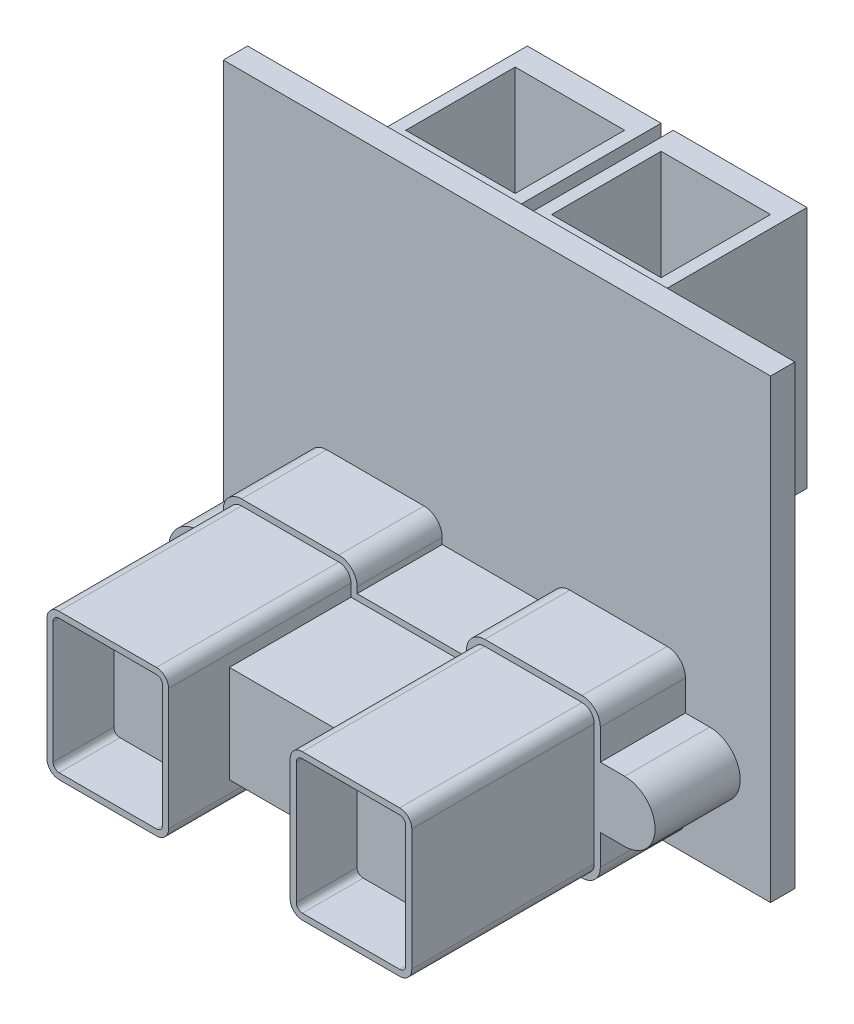
SolidWorks part; units mm, degrees
ref_plane "Front Plane" through (0, 0, 0) normal (0, 0, 1) x (1, 0, 0)
ref_plane "Top Plane" through (0, 0, 0) normal (0, 1, 0) x (1, 0, 0)
ref_plane "Right Plane" through (0, 0, 0) normal (1, 0, 0) x (0, 0, -1)
sketch "Sketch1" plane through (0, 0, 0) normal (0, 0, 1) x (1, 0, 0)
  line L1 (-22.5, 18.75) -> (22.5, 18.75)
  line L2 (-22.5, 18.75) -> (-22.5, -18.75)
  line L3 (-22.5, -18.75) -> (22.5, -18.75)
  line L4 (22.5, 18.75) -> (22.5, -18.75)
  line L5 (-22.5, 18.75) -> (22.5, -18.75) construction
  line L6 (-22.5, -18.75) -> (22.5, 18.75) construction
  point P0 (0, 0)
  dimension "D1" = 37.5
  dimension "D2" = 45
extrude "Boss-Extrude1" add sketch "Sketch1" along normal blind 2
sketch "Sketch2" plane through (0, 0, 2) normal (0, 0, 1) x (1, 0, 0)
  line L0 (0, 18.75) -> (0, -18.75) construction
  line L1 (22.5, 18.75) -> (-22.5, 18.75) construction
  line L2 (-22.5, -18.75) -> (22.5, -18.75) construction
  line L4 (-20, -4.75) -> (20, -4.75)
  line L5 (-20, -4.75) -> (-20, -17.75)
  line L6 (-20, -17.75) -> (20, -17.75)
  line L7 (20, -4.75) -> (20, -17.75)
  line L8 (-20, -4.75) -> (20, -17.75) construction
  line L9 (-20, -17.75) -> (20, -4.75) construction
  point P6 (0, -11.25)
  dimension "D1" = 13
  dimension "D2" = 40
  dimension "D3" = 1
extrude "Boss-Extrude2" add sketch "Sketch2" along normal blind 7
sketch "Sketch3" plane through (0, 0, 9) normal (0, 0, 1) x (1, 0, 0)
  line L0 (0, -4.75) -> (0, -17.75) construction
  line L1 (20, -4.75) -> (-20, -4.75) construction
  line L2 (-20, -17.75) -> (20, -17.75) construction
  line L3 (-5, -7.25) -> (-5, -5.25)
  line L4 (5, -5.25) -> (15, -5.25)
  line L5 (5, -7.25) -> (5, -5.25)
  line L6 (5, -17.25) -> (15, -17.25)
  line L7 (15, -5.25) -> (15, -17.25)
  line L8 (-5, -5.25) -> (-15, -5.25)
  line L9 (5, -15.25) -> (5, -17.25)
  line L10 (-5, -17.25) -> (-15, -17.25)
  line L11 (-15, -5.25) -> (-15, -17.25)
  line L12 (5, -7.25) -> (-5, -7.25)
  line L13 (-5, -15.25) -> (-5, -17.25)
  line L14 (5, -15.25) -> (-5, -15.25)
  line L15 (-20, -17.75) -> (20, -17.75) construction
  point P20 (0, -7.25)
  point P24 (0, -15.25)
  dimension "D1" = 0.5
  dimension "D2" = 0.5
  dimension "D3" = 30
  dimension "D5" = 10
  dimension "D6" = 2
  dimension "D7" = 2
extrude "Boss-Extrude3" add sketch "Sketch3" along normal blind 15
fillet "Fillet1" radius 1 8 edges at (-15, -17.25, 16.5) (-5, -17.25, 16.5) (5, -17.25, 16.5) (-15, -5.25, 16.5) (15, -17.25, 16.5) (15, -5.25, 16.5) (5, -5.25, 16.5) (-5, -5.25, 16.5)
sketch "Sketch4" plane through (0, 0, 24) normal (0, 0, 1) x (1, 0, 0)
  line L0 (-5.5, -14.75) -> (-5.5, -7.75)
  line L1 (5.5, -7.75) -> (5.5, -14.75)
  line L2 (5, -7.25) -> (5, -15.25)
  line L3 (5, -15.25) -> (-5, -15.25)
  line L4 (-5, -15.25) -> (-5, -7.25)
  line L5 (-5, -7.25) -> (5, -7.25)
  line L48 (-14.5, -6.25) -> (-14.5, -16.25)
  line L49 (-14, -16.75) -> (-6, -16.75)
  line L50 (-5.5, -16.25) -> (-5.5, -14.75)
  line L51 (-5.5, -14.75) -> (5.5, -14.75)
  line L52 (5.5, -14.75) -> (5.5, -16.25)
  line L53 (6, -16.75) -> (14, -16.75)
  line L54 (14.5, -16.25) -> (14.5, -6.25)
  line L55 (14, -5.75) -> (6, -5.75)
  line L56 (5.5, -6.25) -> (5.5, -7.75)
  line L57 (5.5, -7.75) -> (-5.5, -7.75)
  line L58 (-5.5, -7.75) -> (-5.5, -6.25)
  line L59 (-6, -5.75) -> (-14, -5.75)
  line L60 (-14.5, -6.25) -> (-14.5, -16.25)
  line L61 (-14, -16.75) -> (-6, -16.75)
  line L62 (-5.5, -16.25) -> (-5.5, -14.75)
  line L63 (-5.5, -14.75) -> (5.5, -14.75) construction
  line L64 (5.5, -14.75) -> (5.5, -16.25)
  line L65 (6, -16.75) -> (14, -16.75)
  line L66 (14.5, -16.25) -> (14.5, -6.25)
  line L67 (14, -5.75) -> (6, -5.75)
  line L68 (5.5, -6.25) -> (5.5, -7.75)
  line L69 (5.5, -7.75) -> (-5.5, -7.75) construction
  line L70 (-5.5, -7.75) -> (-5.5, -6.25)
  line L71 (-6, -5.75) -> (-14, -5.75)
  arc A32 (-14.5, -16.25) -> (-14, -16.75) centre (-14, -16.25) ccw
  arc A33 (-6, -16.75) -> (-5.5, -16.25) centre (-6, -16.25) ccw
  arc A34 (5.5, -16.25) -> (6, -16.75) centre (6, -16.25) ccw
  arc A35 (14, -16.75) -> (14.5, -16.25) centre (14, -16.25) ccw
  arc A36 (14.5, -6.25) -> (14, -5.75) centre (14, -6.25) ccw
  arc A37 (6, -5.75) -> (5.5, -6.25) centre (6, -6.25) ccw
  arc A38 (-5.5, -6.25) -> (-6, -5.75) centre (-6, -6.25) ccw
  arc A39 (-14, -5.75) -> (-14.5, -6.25) centre (-14, -6.25) ccw
  arc A40 (-14.5, -16.25) -> (-14, -16.75) centre (-14, -16.25) ccw
  arc A41 (-6, -16.75) -> (-5.5, -16.25) centre (-6, -16.25) ccw
  arc A42 (5.5, -16.25) -> (6, -16.75) centre (6, -16.25) ccw
  arc A43 (14, -16.75) -> (14.5, -16.25) centre (14, -16.25) ccw
  arc A44 (14.5, -6.25) -> (14, -5.75) centre (14, -6.25) ccw
  arc A45 (6, -5.75) -> (5.5, -6.25) centre (6, -6.25) ccw
  arc A46 (-5.5, -6.25) -> (-6, -5.75) centre (-6, -6.25) ccw
  arc A47 (-14, -5.75) -> (-14.5, -6.25) centre (-14, -6.25) ccw
  dimension "D1" = 0.5
extrude "Cut-Extrude1" cut sketch "Sketch4" against normal blind 5
sketch "Sketch5" plane through (0, 0, 9) normal (0, 0, 1) x (1, 0, 0)
  line L11 (-20, -4.75) -> (-20, -17.75) construction
  line L12 (20, -17.75) -> (20, -4.75) construction
  line L15 (-15.5, -6.25) -> (-15.5, -16.25)
  line L16 (-14, -17.75) -> (-6, -17.75)
  line L17 (6, -17.75) -> (14, -17.75)
  line L18 (-4.5, -15.75) -> (4.5, -15.75)
  line L19 (-4.5, -16.25) -> (-4.5, -15.75)
  line L20 (4.5, -15.75) -> (4.5, -16.25)
  line L21 (-14, -17.75) -> (-6, -17.75)
  line L22 (6, -17.75) -> (14, -17.75)
  line L23 (-4.5, -15.75) -> (4.5, -15.75)
  line L24 (-4.5, -16.25) -> (-4.5, -15.75)
  line L25 (4.5, -15.75) -> (4.5, -16.25)
  line L26 (-15.5, -6.25) -> (-15.5, -16.25) construction
  line L27 (-17.5, -8.75) -> (-15.5, -8.75)
  line L28 (15.5, -16.25) -> (15.5, -6.25)
  line L29 (15.5, -16.25) -> (15.5, -6.25) construction
  line L30 (-15.5, -8.75) -> (-15.5, -6.25)
  line L31 (-17.5, -13.75) -> (-15.5, -13.75)
  line L32 (-15.5, -13.75) -> (-15.5, -16.25)
  line L33 (17.5, -13.75) -> (15.5, -13.75)
  line L34 (15.5, -13.75) -> (15.5, -16.25)
  line L35 (17.5, -8.75) -> (15.5, -8.75)
  line L36 (15.5, -8.75) -> (15.5, -6.25)
  line L51 (20.5, -18.25) -> (20.5, -4.25)
  line L52 (-20.5, -18.25) -> (20.5, -18.25)
  line L53 (-20.5, -4.25) -> (-20.5, -18.25)
  line L54 (20.5, -4.25) -> (-20.5, -4.25)
  line L55 (20.5, -18.25) -> (20.5, -4.25)
  line L56 (-20.5, -18.25) -> (20.5, -18.25)
  line L57 (-20.5, -4.25) -> (-20.5, -18.25)
  line L58 (20.5, -4.25) -> (-20.5, -4.25)
  line L214 (14, -4.75) -> (6, -4.75)
  line L215 (4.5, -6.25) -> (4.5, -6.75)
  line L216 (4.5, -6.75) -> (-4.5, -6.75)
  line L217 (-4.5, -6.75) -> (-4.5, -6.25)
  line L218 (-6, -4.75) -> (-14, -4.75)
  line L219 (14, -4.75) -> (6, -4.75)
  line L220 (4.5, -6.25) -> (4.5, -6.75)
  line L221 (4.5, -6.75) -> (-4.5, -6.75)
  line L222 (-4.5, -6.75) -> (-4.5, -6.25)
  line L223 (-6, -4.75) -> (-14, -4.75)
  circle A4 centre (-17.5, -11.25) radius 2.5 construction
  circle A5 centre (17.5, -11.25) radius 2.5 construction
  arc A6 (-6, -17.75) -> (-4.5, -16.25) centre (-6, -16.25) ccw
  arc A7 (4.5, -16.25) -> (6, -17.75) centre (6, -16.25) ccw
  arc A8 (-6, -17.75) -> (-4.5, -16.25) centre (-6, -16.25) ccw
  arc A9 (4.5, -16.25) -> (6, -17.75) centre (6, -16.25) ccw
  arc A14 (-15.5, -16.25) -> (-14, -17.75) centre (-14, -16.25) ccw
  arc A15 (-14, -4.75) -> (-15.5, -6.25) centre (-14, -6.25) ccw
  arc A16 (-15.5, -16.25) -> (-14, -17.75) centre (-14, -16.25) ccw
  arc A17 (-14, -4.75) -> (-15.5, -6.25) centre (-14, -6.25) ccw
  arc A18 (-17.5, -13.75) -> (-17.5, -8.75) centre (-17.5, -11.25) cw
  arc A19 (17.5, -8.75) -> (17.5, -13.75) centre (17.5, -11.25) cw
  arc A20 (14, -17.75) -> (15.5, -16.25) centre (14, -16.25) ccw
  arc A21 (15.5, -6.25) -> (14, -4.75) centre (14, -6.25) ccw
  arc A22 (14, -17.75) -> (15.5, -16.25) centre (14, -16.25) ccw
  arc A23 (15.5, -6.25) -> (14, -4.75) centre (14, -6.25) ccw
  arc A85 (6, -4.75) -> (4.5, -6.25) centre (6, -6.25) ccw
  arc A86 (-4.5, -6.25) -> (-6, -4.75) centre (-6, -6.25) ccw
  arc A87 (6, -4.75) -> (4.5, -6.25) centre (6, -6.25) ccw
  arc A88 (-4.5, -6.25) -> (-6, -4.75) centre (-6, -6.25) ccw
  point P13 (-20, -11.25)
  dimension "D3" = 5
  dimension "D1" = 0.5
  dimension "D2" = 0.5
  dimension "D4" = 0.5
  dimension "D5" = 0.5
  dimension "D6" = 0.5
extrude "Cut-Extrude2" cut sketch "Sketch5" against normal up to surface (7 mm away) up to face at (0, 0, 2)
sketch "Sketch6" plane through (0, 0, 0) normal (0, 0, -1) x (-1, 0, 0)
  line L0 (0, 18.75) -> (0, -18.75) construction
  line L1 (-22.5, 18.75) -> (22.5, 18.75) construction
  line L2 (22.5, -18.75) -> (-22.5, -18.75) construction
  line L3 (-0.5, 18.25) -> (-0.5, -1.75)
  line L4 (-11.5, 18.25) -> (11.5, 18.25) construction
  line L5 (-11.5, 18.25) -> (-11.5, -1.75)
  line L6 (-11.5, -1.75) -> (11.5, -1.75) construction
  line L7 (11.5, 18.25) -> (11.5, -1.75)
  line L8 (-11.5, 18.25) -> (11.5, -1.75) construction
  line L9 (-11.5, -1.75) -> (11.5, 18.25) construction
  line L10 (-0.5, -1.75) -> (-11.5, -1.75)
  line L11 (-11.5, 18.25) -> (-0.5, 18.25)
  line L12 (11.5, 18.25) -> (0.5, 18.25)
  line L13 (0.5, 18.25) -> (0.5, -1.75)
  line L14 (0.5, -1.75) -> (11.5, -1.75)
  point P6 (0, 8.25)
  dimension "D1" = 20
  dimension "D2" = 23
  dimension "D3" = 11
  dimension "D4" = 0.5
extrude "Boss-Extrude5" add sketch "Sketch6" along normal blind 12
sketch "Sketch7" plane through (0, 18.25, 0) normal (0, 1, 0) x (1, 0, 0)
  line L0 (-11.5, 12) -> (-0.5, 12) construction
  line L1 (-10.5, 10) -> (-1.5, 10)
  line L2 (-10.5, 10) -> (-10.5, 1)
  line L3 (-10.5, 1) -> (-1.5, 1)
  line L4 (-1.5, 10) -> (-1.5, 1)
  line L5 (1.5, 10) -> (10.5, 10)
  line L6 (1.5, 10) -> (1.5, 1)
  line L7 (1.5, 1) -> (10.5, 1)
  line L8 (10.5, 10) -> (10.5, 1)
  line L9 (-11.5, 12) -> (-11.5, 0) construction
  line L10 (-0.5, 12) -> (-0.5, 0) construction
  line L11 (0.5, 12) -> (0.5, 0) construction
  line L12 (0.5, 0) -> (11.5, 0) construction
  dimension "D1" = 2
  dimension "D2" = 1
  dimension "D3" = 1
  dimension "D4" = 1
  dimension "D5" = 1
extrude "Cut-Extrude3" cut sketch "Sketch7" against normal blind 12
